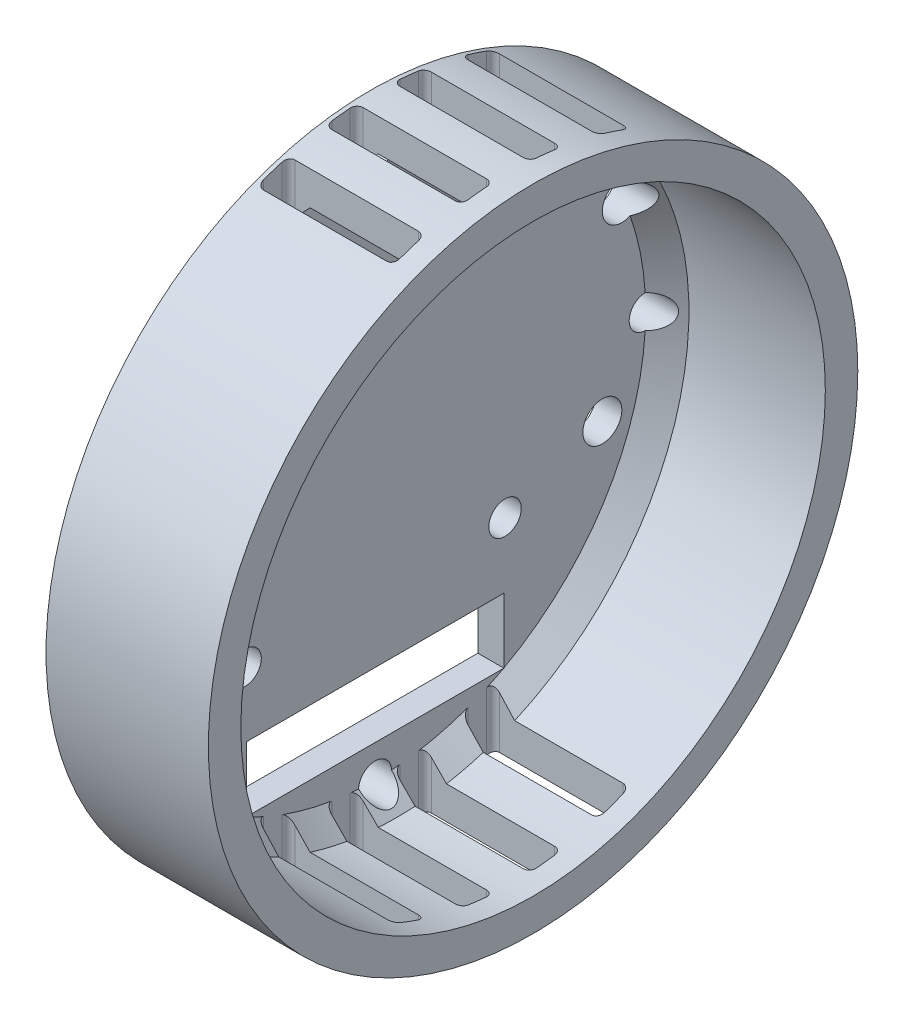
SolidWorks part; units mm, degrees
material "ABS"
ref_plane "Front Plane" through (0, 0, 0) normal (1, 0, 0) x (0, 1, 0)
ref_plane "Top Plane" through (0, 0, 0) normal (0, 0, 1) x (0, 1, 0)
ref_plane "Right Plane" through (0, 0, 0) normal (0, 1, 0) x (-1, 0, 0)
sketch "Sketch1" plane through (0, 0, 0) normal (1, 0, 0) x (0, 1, 0)
  circle A0 centre (0, 0) radius 34.29
  dimension "D1" = 68.58
extrude "Boss-Extrude1" add sketch "Sketch1" along normal blind 2.54
sketch "Sketch2" plane through (2.54, 0, 0) normal (1, 0, 0) x (0, 1, 0)
  circle A0 centre (0, 0) radius 38.1
  dimension "D1" = 76.2
extrude "Boss-Extrude2" add sketch "Sketch2" along normal blind 0.508
sketch "Sketch3" plane through (3.048, 0, 0) normal (1, 0, 0) x (0, 1, 0)
  circle A1 centre (0, 0) radius 38.1
  circle A2 centre (0, 0) radius 34.29
  dimension "D1" = 76.2
  dimension "D2" = 68.58
extrude "Boss-Extrude3" add sketch "Sketch3" along normal blind 18.542
sketch "Sketch5" plane through (3.048, 0, 0) normal (1, 0, 0) x (0, 1, 0)
  circle A0 centre (17.79, 15.25) radius 1.905
  circle A4 centre (17.79, -15.25) radius 1.905
  circle A5 centre (-12.71, -15.25) radius 1.905
  circle A6 centre (-12.71, 15.25) radius 1.905
  point P11 (2.54, 0)
  dimension "D1" = 3.81
  dimension "D2" = 17.79
  dimension "D3" = 15.25
  dimension "D4" = 4
  dimension "D5" = 2.54
extrude "Cut-Extrude1" cut sketch "Sketch5" against normal through all
sketch "Sketch6" plane through (3.048, 0, 0) normal (1, 0, 0) x (0, 1, 0)
  circle A0 centre (28.956, 12.7) radius 2.286
  circle A5 centre (12.7, -28.956) radius 2.286
  circle A7 centre (-12.7, 28.956) radius 2.286
  circle A8 centre (-28.956, -12.7) radius 2.286 [skipped]
  point P12 (0, 0)
  dimension "D2" = 4.572
  dimension "D1" = 12.7
  dimension "D4" = 4
  dimension "D3" = 28.956
extrude "Cut-Extrude10" cut sketch "Sketch6" against normal through all
chamfer "Chamfer2" distance 2.54 angle 45 1 edges at (3.048, 0, -34.29)
sketch "Sketch7" plane through (3.048, 0, 0) normal (1, 0, 0) x (0, 1, 0)
  line L1 (7.9351, 20.32) -> (20.6351, 20.32)
  line L2 (7.9351, 20.32) -> (7.9351, 24.13)
  line L3 (7.9351, 24.13) -> (20.6351, 24.13)
  line L4 (20.6351, 20.32) -> (20.6351, 24.13)
  arc A0 (28.0829, 14.8127) -> (-10.6267, 29.9188) centre (0, 0) ccw construction
  dimension "D1" = 3.81
  dimension "D2" = 12.7
  dimension "D3" = 20.32
extrude "Cut-Extrude11" cut sketch "Sketch7" against normal through all
chamfer "Chamfer3" distance 1.905 angle 45 1 edges at (2.54, 0, -34.29)
sketch "Sketch8" plane through (3.048, 0, 0) normal (1, 0, 0) x (0, 1, 0)
  circle A0 centre (0, -31.75) radius 1.9304
  circle A1 centre (-31.75, 0) radius 1.9304
  circle A2 centre (0, 31.75) radius 1.9304
  circle A3 centre (31.75, 0) radius 1.9304
  point P9 (0, 0)
  dimension "D2" = 3.8608
  dimension "D1" = 31.75
  dimension "D3" = 4
extrude "Cut-Extrude12" cut sketch "Sketch8" against normal through all both and the other way through all
sketch "Sketch9" plane through (3.048, 0, 0) normal (1, 0, 0) x (0, 1, 0)
  line L1 (-27.94, -15.113) -> (-20.32, -15.113)
  line L2 (-27.94, -15.113) -> (-27.94, 15.113)
  line L3 (-27.94, 15.113) -> (-20.32, 15.113)
  line L4 (-20.32, -15.113) -> (-20.32, 15.113)
  line L5 (-27.94, -15.113) -> (-20.32, 15.113) construction
  line L6 (-27.94, 15.113) -> (-20.32, -15.113) construction
  arc A0 (-31.6913, -1.9295) -> (-31.6913, 1.9295) centre (-31.75, 0) ccw construction
  point P0 (-24.13, 0)
  dimension "D3" = 3.81
  dimension "D1" = 7.62
  dimension "D2" = 30.226
extrude "Cut-Extrude13" cut sketch "Sketch9" against normal through all both and the other way through all
sketch "Sketch10" plane through (3.048, 0, 0) normal (1, 0, 0) x (0, 0, -1)
  circle A0 centre (26.67, -8.636) radius 2.286
  arc A1 (31.6913, 1.9295) -> (31.6913, -1.9295) centre (31.75, 0) ccw construction
  dimension "D1" = 4.572
  dimension "D2" = 8.636
  dimension "D3" = 5.08
extrude "Cut-Extrude14" cut sketch "Sketch10" against normal through all both and the other way through all
sketch "Sketch11" plane through (0, -27.94, 0) normal (0, 1, 0) x (-1, 0, 0)
  line L0 (-19.05, 10.16) -> (-19.05, 5.842) construction
  line L1 (-3.81, 13.843) -> (-18.288, 13.843)
  line L2 (-3.048, 13.081) -> (-3.048, 10.922)
  line L3 (-3.81, 10.16) -> (-18.288, 10.16)
  line L4 (-19.05, 13.081) -> (-19.05, 10.922)
  line L5 (-3.81, 5.842) -> (-18.288, 5.842)
  line L6 (-3.048, 5.08) -> (-3.048, 2.921)
  line L7 (-3.81, 2.159) -> (-18.288, 2.159)
  line L8 (-19.05, 5.08) -> (-19.05, 2.921)
  line L9 (-3.81, -2.159) -> (-18.288, -2.159)
  line L10 (-3.048, -2.921) -> (-3.048, -5.08)
  line L11 (-3.81, -5.842) -> (-18.288, -5.842)
  line L12 (-19.05, -2.921) -> (-19.05, -5.08)
  line L13 (-3.81, -10.16) -> (-18.288, -10.16)
  line L14 (-3.048, -10.922) -> (-3.048, -13.081)
  line L15 (-3.81, -13.843) -> (-18.288, -13.843)
  line L16 (-19.05, -10.922) -> (-19.05, -13.081)
  line L17 (-19.05, 2.159) -> (-19.05, -2.159) construction
  line L18 (-19.05, -5.842) -> (-19.05, -10.16) construction
  line L19 (0, 15.113) -> (-3.0635, 15.113) construction
  line L20 (0, -15.113) -> (-3.0635, -15.113) construction
  line L21 (-3.048, 15.0804) -> (-3.048, -15.0804) construction
  line L22 (-21.59, 34.29) -> (-21.59, -34.29) construction
  arc A0 (-3.81, 5.842) -> (-3.048, 5.08) centre (-3.81, 5.08) cw
  arc A1 (-3.048, 2.921) -> (-3.81, 2.159) centre (-3.81, 2.921) cw
  arc A2 (-3.81, -2.159) -> (-3.048, -2.921) centre (-3.81, -2.921) cw
  arc A3 (-3.048, -5.08) -> (-3.81, -5.842) centre (-3.81, -5.08) cw
  arc A4 (-3.81, -10.16) -> (-3.048, -10.922) centre (-3.81, -10.922) cw
  arc A5 (-3.048, -13.081) -> (-3.81, -13.843) centre (-3.81, -13.081) cw
  arc A6 (-18.288, -13.843) -> (-19.05, -13.081) centre (-18.288, -13.081) cw
  arc A7 (-18.288, -10.16) -> (-19.05, -10.922) centre (-18.288, -10.922) ccw
  arc A8 (-18.288, -5.842) -> (-19.05, -5.08) centre (-18.288, -5.08) cw
  arc A9 (-18.288, -2.159) -> (-19.05, -2.921) centre (-18.288, -2.921) ccw
  arc A10 (-18.288, 2.159) -> (-19.05, 2.921) centre (-18.288, 2.921) cw
  arc A11 (-18.288, 5.842) -> (-19.05, 5.08) centre (-18.288, 5.08) ccw
  arc A12 (-18.288, 10.16) -> (-19.05, 10.922) centre (-18.288, 10.922) cw
  arc A13 (-18.288, 13.843) -> (-19.05, 13.081) centre (-18.288, 13.081) ccw
  arc A14 (-3.048, 10.922) -> (-3.81, 10.16) centre (-3.81, 10.922) cw
  arc A15 (-3.81, 13.843) -> (-3.048, 13.081) centre (-3.81, 13.081) cw
  point P63 (-19.05, -1.3316)
  dimension "D4" = 0.762
  dimension "D1" = 1.27
  dimension "D2" = 1.27
  dimension "D3" = 2.54
  dimension "D5" = 4.318
extrude "Cut-Extrude15" cut sketch "Sketch11" against normal through all both and the other way through all
